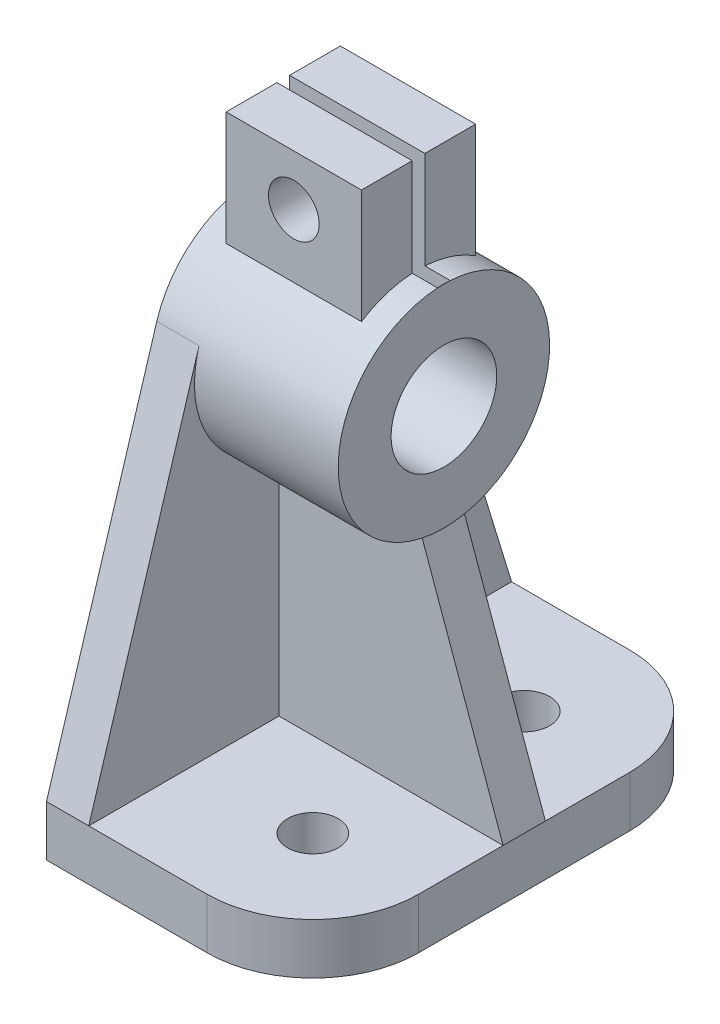
SolidWorks part; units mm, degrees
material "Brass"
ref_plane "Front Plane" through (0, 0, 0) normal (0, 0, 1) x (1, 0, 0)
ref_plane "Top Plane" through (0, 0, 0) normal (0, 1, 0) x (1, 0, 0)
ref_plane "Right Plane" through (0, 0, 0) normal (1, 0, 0) x (0, 0, -1)
sketch "Sketch1" plane through (0, 0, 0) normal (0, 1, 0) x (1, 0, 0)
  line L1 (-31.5, 50) -> (31.5, 50)
  line L2 (-31.5, 50) -> (-31.5, -50)
  line L3 (-31.5, -50) -> (31.5, -50)
  line L4 (31.5, 50) -> (31.5, -50)
  line L5 (-31.5, 50) -> (31.5, -50) construction
  line L6 (-31.5, -50) -> (31.5, 50) construction
  point P0 (0, 0)
  dimension "D1" = 63
  dimension "D2" = 100
extrude "Boss-Extrude1" add sketch "Sketch1" along normal blind 12
fillet "Fillet1" radius 25 2 edges at (31.5, 6, -50) (31.5, 6, 50)
sketch "Sketch2" plane through (0, 12, 0) normal (0, 1, 0) x (1, 0, 0)
  circle A0 centre (6.5, 25) radius 6
  circle A1 centre (6.5, -25) radius 6
  dimension "D1" = 12
  dimension "D2" = 12
extrude "Cut-Extrude1" cut sketch "Sketch2" against normal through all
sketch "Sketch5" plane through (-31.5, 0, 0) normal (-1, 0, 0) x (0, 0, 1)
  line L0 (0, 0) -> (0, 90) construction
  line L1 (-50, 12) -> (50, 12) construction
  line L2 (-50, 12) -> (50, 12)
  line L3 (-50, 12) -> (-23.9068, 97.312)
  line L4 (50, 12) -> (23.9068, 97.312)
  circle A0 centre (0, 90) radius 12.5
  circle A1 centre (0, 90) radius 25
  point P9 (0, 0)
  line M7 (50, 12) -> (-50, 12)
  dimension "D2" = 25
  dimension "D3" = 50
  dimension "D1" = 90
extrude "Boss-Extrude4" add sketch "Sketch5" against normal blind 10 contours L2 L0 A1 L3 | L0 L4 A1 M7 | A1 A0 | A0 region at (-31.5, 40.5565, -21.4549) region at (-31.5, 40.5565, 21.4549) region at (-31.5, 98.5888, -8.5888) region at (-31.5, 75.5512, -19.5288)
extrude "Boss-Extrude5" add sketch "Sketch5<4>" against normal blind 44 contours A0 | A1
sketch "Sketch5<4>" plane through (-31.5, 0, 0) normal (-1, 0, 0) x (0, 0, 1) same geometry as "Sketch5"
sketch "Sketch6" plane through (0, 0, 0) normal (0, 0, 1) x (1, 0, 0)
  line L0 (12.5, 65) -> (31.5, 12)
  line L1 (12.5, 65) -> (12.5, 115) construction
rib "Rib1" sketch "Sketch6" sketch "Sketch6" thickness 10 extrusion direction parallel to sketch draft on no parameters "D1"=10
extrude "Cut-Extrude2" cut sketch "Sketch5<5>" against normal through all contours A0
sketch "Sketch5<5>" plane through (-31.5, 0, 0) normal (-1, 0, 0) x (0, 0, 1) same geometry as "Sketch5"
ref_plane "Plane2" through (0, 138, 0) normal (0, 1, 0) x (1, 0, 0)
sketch "Sketch8" plane through (0, 138, 0) normal (0, 1, 0) x (1, 0, 0)
  line L0 (0, 0) -> (12.5, 0) construction
  line L1 (0, 0) -> (-31.5, 0) construction
  line L2 (-31.5, 23.9068) -> (-31.5, -23.9068) construction
  line L3 (12.5, -25) -> (12.5, 25) construction
  line L4 (6.5, 13.5) -> (-25.5, 13.5)
  line L5 (6.5, 13.5) -> (6.5, -13.5)
  line L6 (6.5, -13.5) -> (-25.5, -13.5)
  line L7 (-25.5, 13.5) -> (-25.5, -13.5)
  line L8 (6.5, 13.5) -> (-25.5, -13.5) construction
  line L9 (6.5, -13.5) -> (-25.5, 13.5) construction
  point P4 (-9.5, 0)
  dimension "D1" = 32
  dimension "D2" = 27
  dimension "D3" = 6
extrude "Boss-Extrude6" add sketch "Sketch8" against normal up to next
sketch "Sketch9" plane through (0, 138, 0) normal (0, 1, 0) x (1, 0, 0)
  line L0 (6.5, 0) -> (-25.5, 0) construction
  line L1 (6.5, -13.5) -> (6.5, 13.5) construction
  line L2 (-25.5, 13.5) -> (-25.5, -13.5) construction
  line L4 (-31.4804, 1.5) -> (12.4804, 1.5)
  line L5 (-31.4804, 1.5) -> (-31.4804, -1.5)
  line L6 (-31.4804, -1.5) -> (12.4804, -1.5)
  line L7 (12.4804, 1.5) -> (12.4804, -1.5)
  line L8 (-31.4804, 1.5) -> (12.4804, -1.5) construction
  line L9 (-31.4804, -1.5) -> (12.4804, 1.5) construction
  point P6 (-9.5, 0)
  dimension "D1" = 3
extrude "Cut-Extrude3" cut sketch "Sketch9" against normal up to next
sketch "Sketch10" plane through (0, 0, -13.5) normal (0, 0, -1) x (-1, 0, 0)
  line L0 (25.5, 111.0416) -> (25.5, 138) construction
  line L1 (-6.5, 138) -> (25.5, 138) construction
  circle A0 centre (9.5, 126) radius 6
  point P6 (70.9519, 96.44)
  point P11 (-29.1386, 123.8799)
  dimension "D1" = 12
  dimension "D2" = 16
  dimension "D3" = 12
extrude "Cut-Extrude4" cut sketch "Sketch10" against normal through all both and the other way through all
